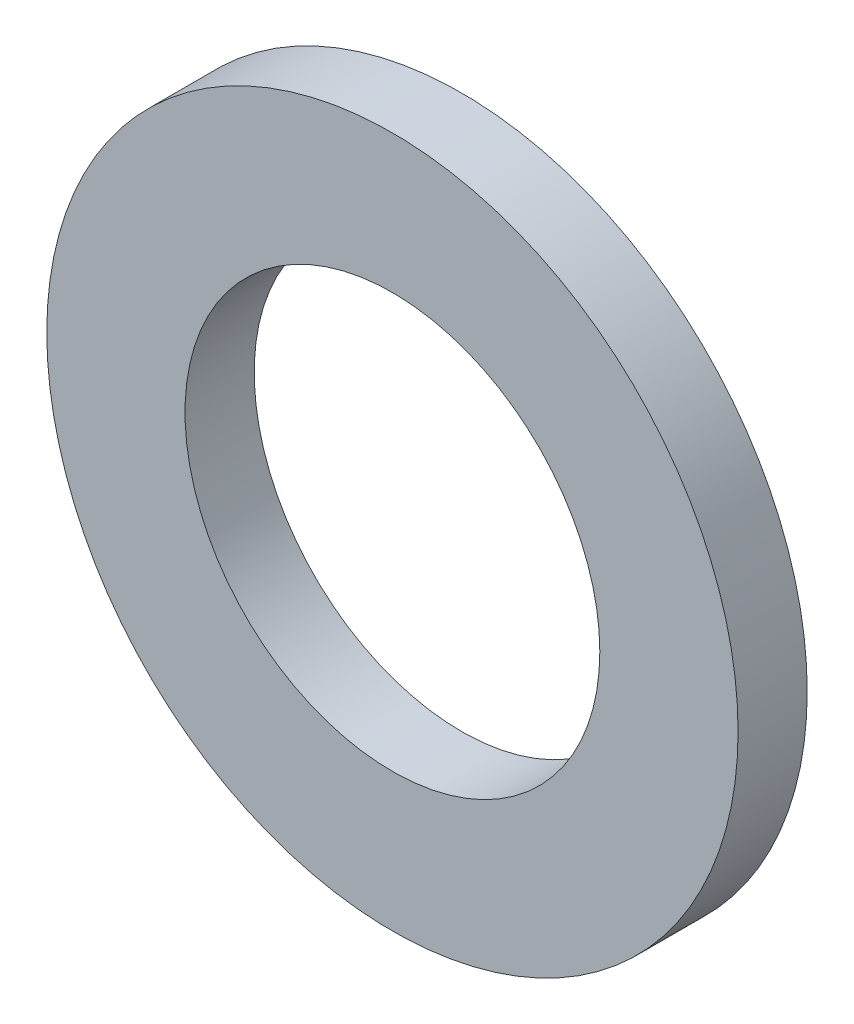
SolidWorks part; units mm, degrees
ref_plane "Front Plane" through (0, 0, 0) normal (0, 0, 1) x (1, 0, 0)
ref_plane "Top Plane" through (0, 0, 0) normal (0, 1, 0) x (1, 0, 0)
ref_plane "Right Plane" through (0, 0, 0) normal (1, 0, 0) x (0, 0, -1)
sketch "Sketch1" plane through (0, 0, 0) normal (0, 0, 1) x (1, 0, 0)
  circle A0 centre (0, 0) radius 10
  circle A1 centre (0, 0) radius 6
  dimension "D1" = 20
  dimension "ID" = 12
extrude "Extrude1" add sketch "Sketch1" along normal mid plane 2
sketch "Sketch2" plane through (0, 0, 0) normal (1, 0, 0) x (0, 0, -1)
  line L0 (-1, -6) -> (1, -6) construction
  line L3 (1, 6) -> (-1, 6) construction
  line L5 (-1, -6) -> (1, -6)
  line L6 (1, 6) -> (-1, 6)
sketch "Sketch4" plane through (0, 0, 1) normal (0, 0, 1) x (1, 0, 0)
  line L0 (0, 0) -> (-4.2426, 4.2426)
  line L1 (0, -1.1) -> (0, 1.1) construction
  circle A0 centre (0, 0) radius 6 construction
  dimension "D1" = 45
ref_axis "Center Axis 1" through (0, 0, 1) along (0, 0, -1)
ref_plane "Contact Plane 1" through (0, 0, 1) normal (0, 0, 1) x (1, 0, 0)
ref_plane "Contact Plane 2" through (0, 0, -1) normal (0, 0, -1) x (-1, 0, 0)
